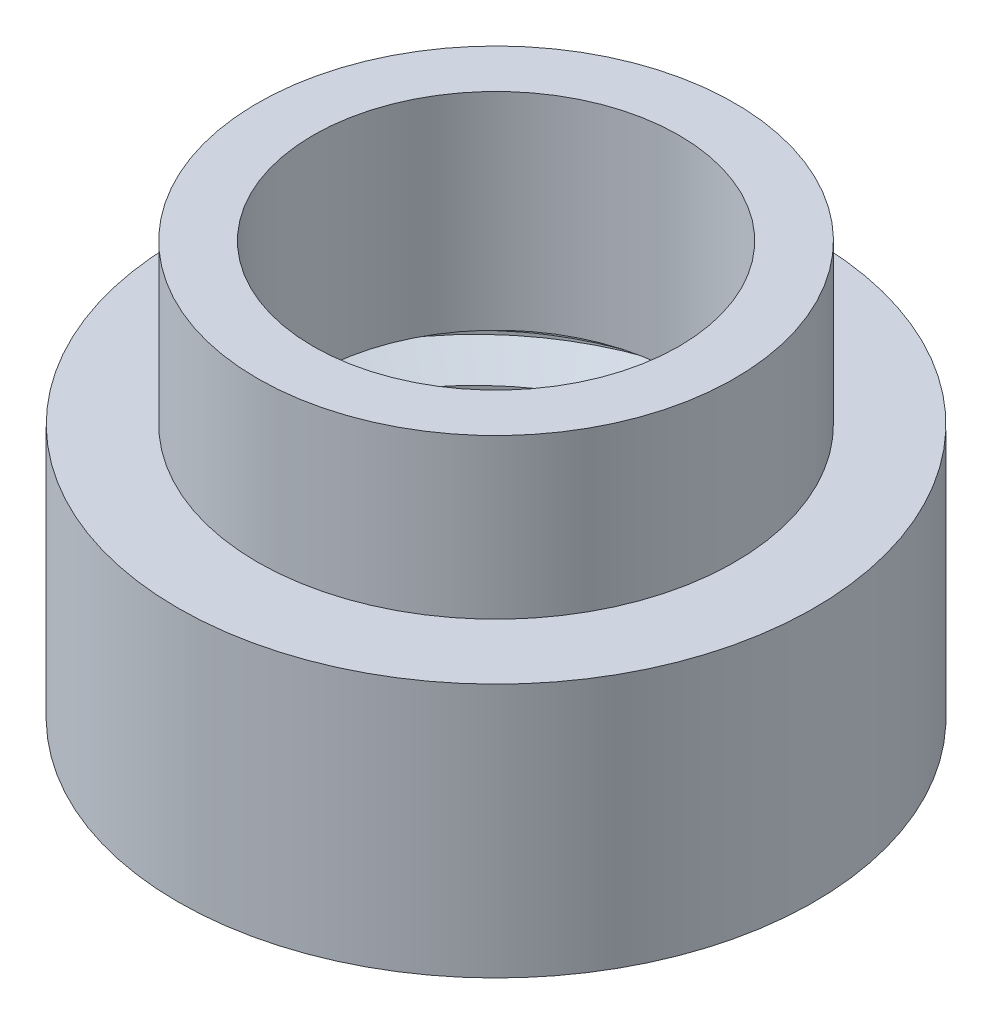
SolidWorks part; units mm, degrees
ref_plane "Front Plane" through (0, 0, 0) normal (0, 0, 1) x (1, 0, 0)
ref_plane "Top Plane" through (0, 0, 0) normal (0, 1, 0) x (1, 0, 0)
ref_plane "Right Plane" through (0, 0, 0) normal (1, 0, 0) x (0, 0, -1)
sketch "Sketch1" plane through (0, 0, 0) normal (1, 0, 0) x (0, 0, -1)
  line L0 (0, 15.0909) -> (0, -14.5909) construction
  line L1 (-7.5, 2.5) -> (-7.5, -4)
  line L2 (-7.5, -4) -> (-10, -4)
  line L3 (-10, -4) -> (-10, 4)
  line L4 (-10, 4) -> (-7.5, 4)
  line L5 (-7.5, 2.5) -> (-5.75, 2.5)
  line L7 (-7.5, 4) -> (-7.5, 9)
  line L15 (-5.75, 2.5) -> (-5.75, 9)
  line L17 (-7.5, 9) -> (-5.75, 9)
  point P5 (-10, 0)
  dimension "D1" = 15
  dimension "D2" = 20
  dimension "D3" = 8
  dimension "D4" = 6.5
  dimension "D5" = 11.5
  dimension "D6" = 5
  dimension "D7" = 7.5
revolve "Revolve1" add sketch "Sketch1" angle 360 about L0
thread "Thread1" pitch 2 method cut profile "Thread Profile1" start angle 0, offset 5, length 10, pitch 2, diameter 15
ref_plane "Plane1" through (7.5, -9, 0) normal (0, 0, 1) x (1, 0, 0)
sketch "Thread Profile1" plane through (7.5, -9, 0) normal (0, 0, 1) x (1, 0, 0)
  line L0 (0, 0) -> (0, 2) construction
  line L1 (0, 0) -> (1.0825, 0.625)
  line L2 (1.0825, 0.625) -> (1.0825, 0.875)
  line L3 (1.0825, 0.875) -> (0, 1.5)
  line L4 (1.0825, 0.75) -> (0, 0.75) construction
  line L11 (0, 0) -> (0, 1.5)
  point P2 (0, 0)
  dimension "Pitch" = 2
  dimension "Profile_Angle" = 60
  dimension "Profile_Land" = 0.25
  dimension "Profile_Height" = 1.0825
